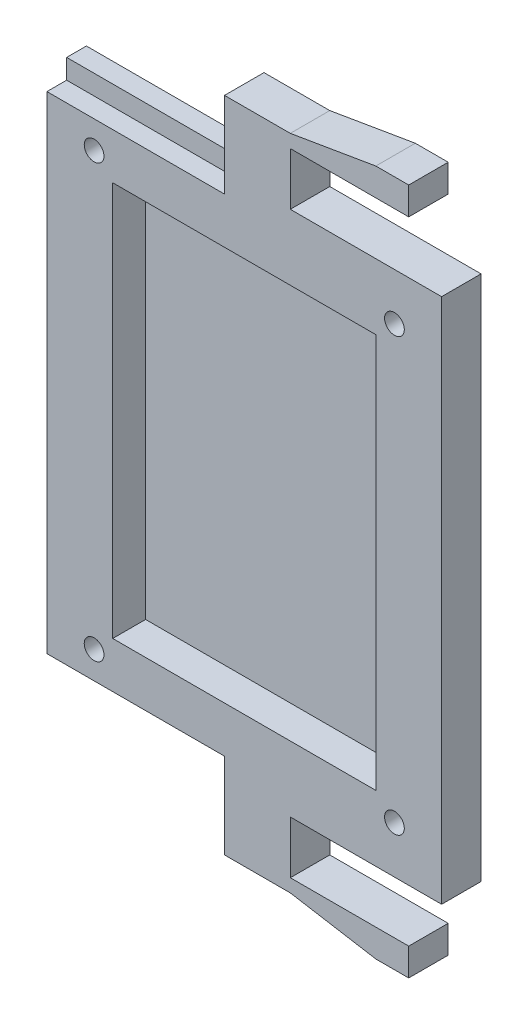
SolidWorks part; units mm, degrees
ref_plane "Front Plane" through (0, 0, 0) normal (1, 0, 0) x (0, 1, 0)
ref_plane "Top Plane" through (0, 0, 0) normal (0, 0, 1) x (0, 1, 0)
ref_plane "Right Plane" through (0, 0, 0) normal (0, 1, 0) x (-1, 0, 0)
sketch "Sketch1" plane through (0, 0, 0) normal (0, 0, 1) x (0, 1, 0)
  line L0 (-40, -7) -> (-48, -7)
  line L1 (-40, -30) -> (40, -30)
  line L2 (-40, -30) -> (-40, -7)
  line L3 (-40, 30) -> (40, 30)
  line L4 (40, -30) -> (40, -7)
  line L5 (-40, -30) -> (40, 30) construction
  line L6 (-40, 30) -> (40, -30) construction
  line L9 (-52.2, -20) -> (-50, -7)
  line L13 (-52.2, -20) -> (-52.2, -25)
  line L14 (-52.2, -25) -> (-48, -25)
  line L15 (-48, -7) -> (-48, -25)
  line L17 (-50, -7) -> (-48, -7) construction
  line L18 (-40, 30) -> (-40, -13.0472) construction
  line L19 (0, 30) -> (0, -30) construction
  line L28 (-50, 3) -> (-40, 3)
  line L29 (-40, 3) -> (-40, 30)
  line L30 (50, 3) -> (40, 3)
  line L31 (40, -7) -> (48, -7)
  line L32 (50, -7) -> (48, -7) construction
  line L35 (48, -7) -> (48, -25)
  line L36 (52.2, -25) -> (48, -25)
  line L37 (52.2, -20) -> (52.2, -25)
  line L39 (52.2, -20) -> (50, -7)
  line L40 (40, 30) -> (40, 3)
  line L41 (-50, -7) -> (-50, 3)
  line L42 (50, 3) -> (50, -7)
  point P1 (0, 0)
  point P8 (50, -6.9939)
  dimension "D1" = 80
  dimension "D2" = 60
  dimension "D3" = 18
  dimension "D4" = 10
  dimension "D5" = 5
  dimension "D6" = 5
  dimension "D7" = 2
  dimension "D8" = 4.2
  dimension "D9" = 10
extrude "Boss-Extrude1" add sketch "Sketch1" along normal blind 6
sketch "Sketch3" plane through (0, 0, 6) normal (0, 0, 1) x (1, 0, 0)
  line L0 (0, 0) -> (20, 0) construction
  line L1 (-20, -30) -> (20, -30)
  line L2 (-20, -30) -> (-20, 30)
  line L3 (-20, 30) -> (20, 30)
  line L4 (20, -30) -> (20, 30)
  line L5 (-20, -30) -> (20, 30) construction
  line L6 (-20, 30) -> (20, -30) construction
  line L8 (20, 30) -> (30, 40) construction
  line L9 (0, 30) -> (0, 0) construction
  circle A0 centre (22.8284, 32.8284) radius 1.5
  circle A1 centre (-22.8284, 32.8284) radius 1.5
  circle A2 centre (22.8284, -32.8284) radius 1.5
  circle A3 centre (-22.8284, -32.8284) radius 1.5
  point P0 (0, 0)
  point P20 (25, 35)
  dimension "D3" = 3
  dimension "D1" = 40
  dimension "D2" = 60
  dimension "D4" = 4
extrude "Cut-Extrude1" cut sketch "Sketch3" against normal blind 5
sketch "Sketch4" plane through (-30, 0, 0) normal (-1, 0, 0) x (0, -1, 0)
  line L0 (0, 6) -> (0, 0) construction
  line L1 (-40, 6) -> (-37, 6)
  line L2 (-40, 6) -> (-40, 3)
  line L3 (-40, 3) -> (-37, 3)
  line L4 (-37, 6) -> (-37, 3)
  line L5 (-40, 6) -> (40, 6) construction
  line L6 (40, 3) -> (37, 3)
  line L7 (37, 6) -> (37, 3)
  line L8 (40, 6) -> (37, 6)
  line L9 (40, 6) -> (40, 3)
  dimension "D1" = 3
  dimension "D2" = 3
extrude "Cut-Extrude2" cut sketch "Sketch4" against normal up to surface (27 mm away) up to face at (-3, 45, 3)
